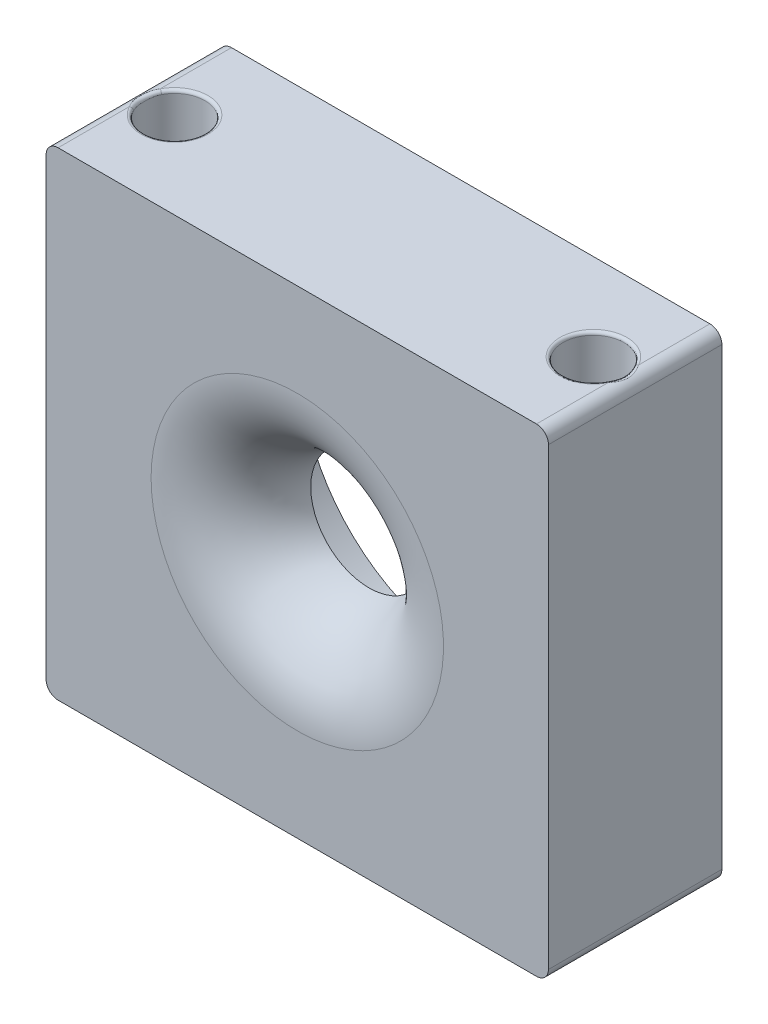
SolidWorks part; units mm, degrees
ref_plane "Front Plane" through (0, 0, 0) normal (1, 0, 0) x (0, 1, 0)
ref_plane "Top Plane" through (0, 0, 0) normal (0, 0, 1) x (0, 1, 0)
ref_plane "Right Plane" through (0, 0, 0) normal (0, 1, 0) x (-1, 0, 0)
sketch "Sketch1" plane through (0, 0, 0) normal (0, 0, 1) x (0, 1, 0)
  line L1 (-40, -42) -> (40, -42)
  line L2 (-40, -42) -> (-40, 42)
  line L3 (-40, 42) -> (40, 42)
  line L4 (40, -42) -> (40, 42)
  line L5 (-40, -42) -> (40, 42) construction
  line L6 (-40, 42) -> (40, -42) construction
  circle A0 centre (0, 0) radius 9.75
  point P0 (0, 0)
  dimension "D3" = 19.5
  dimension "D1" = 84
  dimension "D2" = 80
extrude "Main Boss" add sketch "Sketch1" along normal blind 29
sketch "Sketch2" plane through (0, 0, 0) normal (0, 0, -1) x (1, 0, 0)
  circle A0 centre (0, 0) radius 28.5
  dimension "D1" = 57
extrude "Cut-Extrude1" cut sketch "Sketch2" against normal blind 17
fillet "Fillet1" radius 15 1 edges at (9.75, 0, 29)
sketch "Sketch3" plane through (0, 40, 0) normal (0, 1, 0) x (-1, 0, 0)
  line L0 (-42, 14.5) -> (42, 14.5) construction
  line L1 (-42, 29) -> (-42, 0) construction
  line L2 (42, 29) -> (42, 0) construction
  line L3 (0, 29) -> (0, 0) construction
  line L4 (-42, 29) -> (42, 29) construction
  line L5 (-42, 14.5) -> (-40.125, 14.5)
  circle A0 centre (-35.025, 14.5) radius 5.1
  circle A1 centre (35.025, 14.5) radius 5.1
  dimension "D1" = 10.2
extrude "Screw Head" cut sketch "Sketch3" against normal blind 38 contours A0 | A1 region at (35.025, 40, 14.5) region at (-35.025, 40, 14.5)
sketch "Sketch4" plane through (0, 40, 0) normal (0, 1, 0) x (-1, 0, 0)
  line L1 (-30.3244, 17.8523) -> (-35.5779, 20.247)
  line L2 (-35.5779, 20.247) -> (-40.2785, 16.8947)
  line L3 (-40.2785, 16.8947) -> (-39.7256, 11.1477)
  line L4 (-39.7256, 11.1477) -> (-34.4721, 8.753)
  line L5 (-34.4721, 8.753) -> (-29.7715, 12.1053)
  line L6 (-29.7715, 12.1053) -> (-30.3244, 17.8523)
  circle A0 centre (-35.025, 14.5) radius 5 construction
  circle A1 centre (-35.025, 14.5) radius 5.1 construction
extrude "Nut Slot" cut sketch "Sketch4" against normal blind 4.8 from offset 42 offset against normal yes
sketch "Sketch5" plane through (0, 40, 0) normal (0, 1, 0) x (-1, 0, 0)
  circle A0 centre (-35.025, 14.5) radius 3.2
  circle A1 centre (-35.025, 14.5) radius 5.1 construction
  dimension "D1" = 6.4
extrude "Through Hole" cut sketch "Sketch5" against normal through all
mirror "Mirror2" about plane through (0, 0, 0) normal (1, 0, 0) of "Through Hole", "Nut Slot"
fillet "Fillet2" radius 3 1 edges at (-28.5, 0, 17)
fillet "Fillet3" radius 2 4 edges at (-42, 40, 14.5) (-42, -40, 14.5) (42, -40, 14.5) (42, 40, 14.5)
fillet "Fillet4" radius 0.5 4 edges at (-40.0911, 39.9979, 15.0869) (40.0911, 39.9979, 13.9131) (-29.925, 40, 14.5) (29.925, 40, 14.5)
